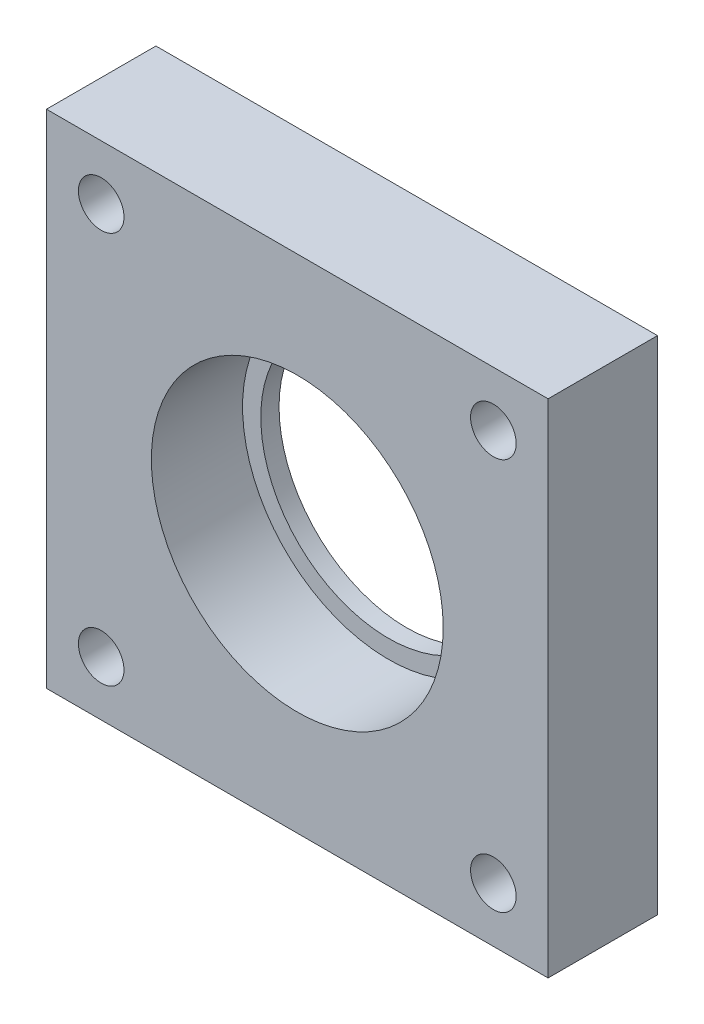
SolidWorks part; units mm, degrees
ref_plane "Piano frontale" through (0, 0, 0) normal (0, 0, 1) x (1, 0, 0)
ref_plane "Piano superiore" through (0, 0, 0) normal (0, 1, 0) x (1, 0, 0)
ref_plane "Piano destro" through (0, 0, 0) normal (1, 0, 0) x (0, 0, -1)
sketch "Schizzo1" plane through (0, 0, 0) normal (0, 0, 1) x (1, 0, 0)
  line L1 (0, 0) -> (55, 0)
  line L2 (0, 0) -> (0, 55)
  line L3 (0, 55) -> (55, 55)
  line L4 (55, 0) -> (55, 55)
  dimension "D1" = 55
  dimension "D2" = 55
extrude "Estrusione-Estrusione1" add sketch "Schizzo1" against normal blind 12
sketch "Schizzo2" plane through (0, 0, 0) normal (0, 0, 1) x (1, 0, 0)
  line L0 (0, 27.5) -> (55, 27.5) construction
  line L1 (0, 55) -> (0, 0) construction
  line L2 (55, 0) -> (55, 55) construction
  circle A0 centre (27.5, 27.5) radius 16
  dimension "D1" = 32
extrude "Taglio-Estrusione1" cut sketch "Schizzo2" against normal blind 10
sketch "Schizzo3" plane through (0, 0, -10) normal (0, 0, 1) x (1, 0, 0)
  line L0 (0, 27.5) -> (55, 27.5) construction
  line L1 (0, 55) -> (0, 0) construction
  line L2 (55, 0) -> (55, 55) construction
  circle A0 centre (27.5, 27.5) radius 14
  dimension "D1" = 28
extrude "Taglio-Estrusione2" cut sketch "Schizzo3" against normal blind 10
sketch "Schizzo4" plane through (0, 0, 0) normal (0, 0, 1) x (1, 0, 0)
  line L0 (0, 27.5) -> (55, 27.5) construction
  line L1 (0, 55) -> (0, 0) construction
  line L2 (55, 0) -> (55, 55) construction
  line L3 (0, 55) -> (0, 27.5) construction
  line L4 (55, 55) -> (0, 55) construction
  line L5 (27.5, 55) -> (27.5, 0) construction
  line L6 (0, 0) -> (55, 0) construction
  line L7 (0, 55) -> (27.5, 55) construction
  line L8 (6, 55) -> (6, 27.5) construction
  line L9 (0, 49) -> (27.5, 49) construction
  circle A0 centre (6, 49) radius 2.5
  circle A1 centre (49, 49) radius 2.5
  circle A2 centre (49, 6) radius 2.5
  circle A3 centre (6, 6) radius 2.5
  circle A4 centre (27.5, 27.5) radius 30.4056 construction
  point P16 (27.5, 27.5)
  dimension "D3" = 5
  dimension "D4" = 30.4056
  dimension "D1" = 6
  dimension "D2" = 6
extrude "Taglio-Estrusione3" cut sketch "Schizzo4" against normal blind 12
